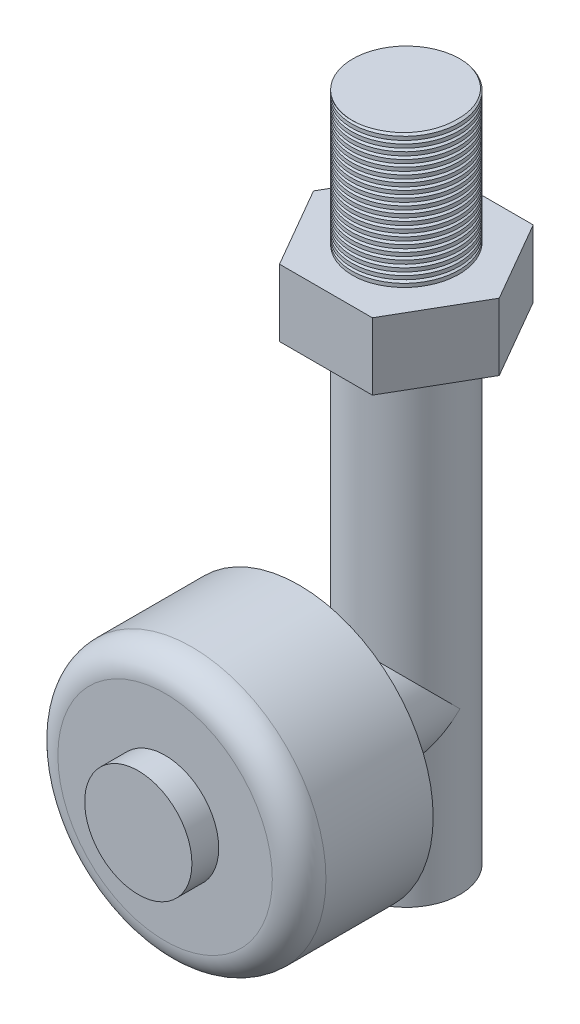
SolidWorks part; units mm, degrees
material "ABS"
ref_plane "Alzado" through (0, 0, 0) normal (0, 0, 1) x (1, 0, 0)
ref_plane "Planta" through (0, 0, 0) normal (0, 1, 0) x (1, 0, 0)
ref_plane "Vista lateral" through (0, 0, 0) normal (1, 0, 0) x (0, 0, -1)
sketch "Croquis1" plane through (0, 0, 0) normal (0, 1, 0) x (1, 0, 0)
  circle A0 centre (0, 0) radius 4
extrude "Saliente-Extruir1" add sketch "Croquis1" along normal blind 35
sketch "Croquis2" plane through (0, 35, 0) normal (0, 1, 0) x (1, 0, 0)
  line L1 (4.1353, -6.9857) -> (7.8637, -2.0156)
  line L2 (7.8637, -2.0156) -> (6.9857, 4.1353)
  line L3 (6.9857, 4.1353) -> (2.0156, 7.8637)
  line L4 (2.0156, 7.8637) -> (-4.1353, 6.9857)
  line L5 (-4.1353, 6.9857) -> (-7.8637, 2.0156)
  line L6 (-7.8637, 2.0156) -> (-6.9857, -4.1353)
  line L7 (-6.9857, -4.1353) -> (-2.0156, -7.8637)
  line L8 (-2.0156, -7.8637) -> (4.1353, -6.9857)
  circle A0 centre (0, 0) radius 7.5 construction
extrude "Saliente-Extruir3" add sketch "Croquis2" along normal blind 5
sketch "Croquis3" plane through (0, 0, 0) normal (0, 0, 1) x (1, 0, 0)
  line L0 (0, 0) -> (0, 8) construction
  circle A0 centre (0, 12) radius 4
  dimension "D1" = 4
extrude "Saliente-Extruir4" add sketch "Croquis3" along normal blind 20
sketch "Croquis4" plane through (0, 0, 20) normal (0, 0, 1) x (1, 0, 0)
  circle A0 centre (0, 12) radius 10
extrude "Saliente-Extruir7" add sketch "Croquis4" against normal blind 12
sketch "Croquis6" plane through (0, 0, 20) normal (0, 0, 1) x (1, 0, 0)
  circle A0 centre (0, 12) radius 10
extrude "Cortar-Extruir2" cut sketch "Croquis6" against normal blind 2
sketch "Croquis7" plane through (0, 0, 18) normal (0, 0, 1) x (1, 0, 0)
  circle A0 centre (0, 12) radius 4
extrude "Saliente-Extruir8" add sketch "Croquis7" along normal blind 2
sketch "Croquis9" plane through (0, 40, 0) normal (0, 1, 0) x (1, 0, 0)
  line L1 (-13.4731, 14.1749) -> (14.607, 14.1749)
  line L2 (-13.4731, 14.1749) -> (-13.4731, -10.1701)
  line L3 (-13.4731, -10.1701) -> (14.607, -10.1701)
  line L4 (14.607, 14.1749) -> (14.607, -10.1701)
extrude "Cortar-Extruir3" cut sketch "Croquis9" against normal blind 5
sketch "Croquis10" plane through (0, 35, 0) normal (0, 1, 0) x (1, 0, 0)
  line L1 (6.9282, 0) -> (3.4641, 6)
  line L2 (3.4641, 6) -> (-3.4641, 6)
  line L3 (-3.4641, 6) -> (-6.9282, 0)
  line L4 (-6.9282, 0) -> (-3.4641, -6)
  line L5 (-3.4641, -6) -> (3.4641, -6)
  line L6 (3.4641, -6) -> (6.9282, 0)
  circle A0 centre (0, 0) radius 6 construction
extrude "Saliente-Extruir9" add sketch "Croquis10" along normal blind 5
sketch "Croquis11" plane through (0, 40, 0) normal (0, 1, 0) x (1, 0, 0)
  circle A0 centre (0, 0) radius 4
extrude "Saliente-Extruir10" add sketch "Croquis11" along normal blind 5
sketch "Croquis12" plane through (0, 45, 0) normal (0, 1, 0) x (1, 0, 0)
  circle A0 centre (0, 0) radius 4
curve "Hélice/Espiral1" pitch 0.5 height 4 turns 8
sketch "Croquis13" plane through (0, 0, 0) normal (0, 0, 1) x (1, 0, 0)
  line L0 (4, 45) -> (-4, 45) construction
  line L1 (4.1, 44.8268) -> (3.8, 45)
  line L2 (3.8, 45) -> (4.1, 45.1732)
  line L3 (4.1, 45.1732) -> (4.1, 44.8268)
  circle A0 centre (4, 45) radius 0.1 construction
sweep "Cortar-Barrer1" cut profiles "Croquis13" path "Hélice/Espiral1"
fillet "Redondeo1" radius 2 1 edges at (10, 12, 18)
sketch "Croquis14" plane through (0, 40, 0) normal (0, 1, 0) x (1, 0, 0)
  circle A0 centre (0, 0) radius 4
extrude "Saliente-Extruir11" add sketch "Croquis14" along normal blind 10
sketch "Croquis15" plane through (0, 50, 0) normal (0, 1, 0) x (1, 0, 0)
  circle A0 centre (0, 0) radius 4
curve "Hélice/Espiral2" pitch 0.5 height 10 turns 20
sketch "Croquis16" plane through (0, 0, 0) normal (0, 0, 1) x (1, 0, 0)
  line L1 (3.8, 50) -> (4.1, 49.8268)
  line L2 (4.1, 49.8268) -> (4.1, 50.1732)
  line L3 (4.1, 50.1732) -> (3.8, 50)
  circle A0 centre (4, 50) radius 0.1 construction
sweep "Cortar-Barrer2" cut profiles "Croquis16" path "Hélice/Espiral2"
